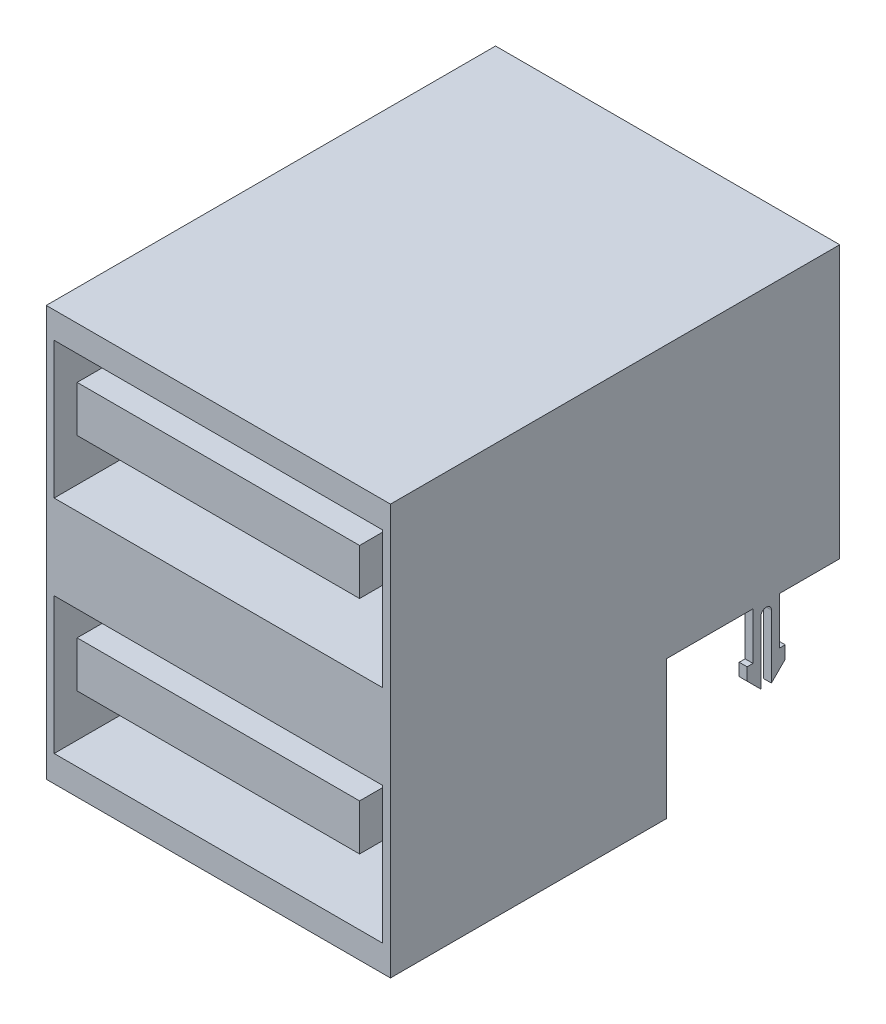
SolidWorks part; units mm, degrees
ref_plane "Front Plane" through (0, 0, 0) normal (0, 0, 1) x (1, 0, 0)
ref_plane "Top Plane" through (0, 0, 0) normal (0, 1, 0) x (1, 0, 0)
ref_plane "Right Plane" through (0, 0, 0) normal (1, 0, 0) x (0, 0, -1)
sketch "Sketch1" plane through (0, 0, 0) normal (1, 0, 0) x (0, 0, -1)
  line L0 (0, 55) -> (0, -55) construction
  line L1 (-10.5, 10.35) -> (6.6, 10.35)
  line L2 (-10.5, 10.35) -> (-10.5, -5.27)
  line L3 (-10.5, -5.27) -> (0, -5.27)
  line L4 (6.6, 10.35) -> (6.6, 0)
  line L5 (55, 0) -> (-55, 0) construction
  line L7 (0, 0) -> (6.6, 0)
  line L8 (0, 0) -> (0, -5.27)
  dimension "D1" = 10.5
  dimension "D2" = 17.1
  dimension "D3" = 10.35
  dimension "D4" = 15.62
extrude "Boss-Extrude1" add sketch "Sketch1" along normal blind 6.55 and the other way blind 6.55
sketch "Sketch2" plane through (0, 0, 10.5) normal (0, 0, 1) x (1, 0, 0)
  line L0 (-6.55, -5.27) -> (6.55, -5.27) construction
  line L1 (-6.25, 9.35) -> (6.25, 9.35)
  line L2 (-6.25, 9.35) -> (-6.25, 4.15)
  line L3 (-6.25, 4.15) -> (6.25, 4.15)
  line L4 (6.25, 9.35) -> (6.25, 4.15)
  line L5 (-6.25, -4.27) -> (6.25, -4.27)
  line L6 (-6.25, -4.27) -> (-6.25, 0.93)
  line L7 (-6.25, 0.93) -> (6.25, 0.93)
  line L8 (6.25, -4.27) -> (6.25, 0.93)
  line L9 (0, -55) -> (0, 55) construction
  line L11 (-5.375, 8.4) -> (5.375, 8.4)
  line L12 (-5.375, 8.4) -> (-5.375, 6.65)
  line L13 (-5.375, 6.65) -> (5.375, 6.65)
  line L14 (5.375, 8.4) -> (5.375, 6.65)
  line L15 (-5.375, -0.02) -> (5.375, -0.02)
  line L16 (-5.375, -0.02) -> (-5.375, -1.77)
  line L17 (-5.375, -1.77) -> (5.375, -1.77)
  line L18 (5.375, -0.02) -> (5.375, -1.77)
  dimension "D1" = 1
  dimension "D2" = 13.62
  dimension "D3" = 6.25
  dimension "D4" = 12.5
  dimension "D5" = 6.25
  dimension "D6" = 12.5
  dimension "D7" = 5.2
  dimension "D8" = 5.2
  dimension "D9" = 2.5
  dimension "D10" = 2.5
  dimension "D11" = 10.75
  dimension "D12" = 5.375
  dimension "D13" = 1.75
  dimension "D14" = 1.75
  dimension "D15" = 10.75
  dimension "D16" = 5.375
extrude "Cut-Extrude1" cut sketch "Sketch2" against normal blind 9.5
sketch "Sketch3" plane through (6.55, 0, 0) normal (1, 0, 0) x (0, 0, -1)
  line L0 (3.8, 0) -> (3.8, -8.0818) construction
  line L1 (7.205, 0) -> (-7.205, 0) construction
  line L2 (-10.5, 10.35) -> (-10.5, -5.27) construction
  line L3 (0.9239, -2.8) -> (3.075, -2.8) construction
  line L4 (3.6, -2.8) -> (3.075, -2.275)
  line L5 (3.3, 0) -> (4.3, 0)
  line L6 (3.075, -1.8) -> (3.075, -2.275)
  line L8 (4.525, -1.8) -> (4.525, -2.275)
  line L10 (3.6, -2.8) -> (3.6, -0.395)
  line L11 (3.795, -0.2) -> (3.805, -0.2)
  line L12 (4, -2.8) -> (4, -0.395)
  line L13 (4, -2.8) -> (4.525, -2.275)
  line L14 (3.075, -1.8) -> (3.3, -1.8)
  line L15 (3.3, -1.8) -> (3.3, 0)
  line L16 (4.525, -1.8) -> (4.3, -1.8)
  line L17 (4.3, -1.8) -> (4.3, 0)
  line L18 (4.525, -2.8) -> (7.2768, -2.8) construction
  arc A0 (4, -0.395) -> (3.805, -0.2) centre (3.805, -0.395) ccw
  arc A1 (3.795, -0.2) -> (3.6, -0.395) centre (3.795, -0.395) ccw
  dimension "D14" = 0.195
  dimension "D1" = 14.3
  dimension "D2" = 2.8
  dimension "D3" = 1.45
  dimension "D4" = 1.45
  dimension "D5" = 0.2
  dimension "D6" = 0.4
  dimension "D7" = 0.2
  dimension "D8" = 0.5
  dimension "D9" = 0.5
  dimension "D10" = 1
  dimension "D11" = 1
  dimension "D12" = 45
  dimension "D13" = 45
  dimension "D15" = 0.525
  dimension "D16" = 0.525
  dimension "D17" = 2.8
extrude "Boss-Extrude2" add sketch "Sketch3" against normal blind 0.3
mirror "Mirror1" about plane through (0, 0, 0) normal (1, 0, 0) of "Boss-Extrude2"
